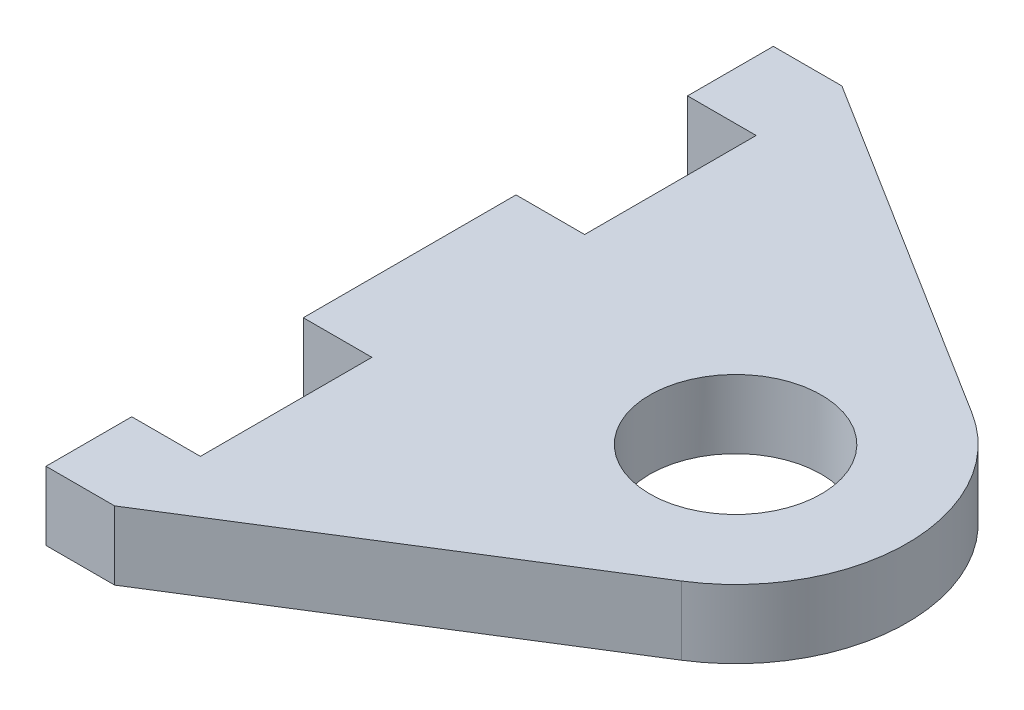
SolidWorks part; units mm, degrees
ref_plane "Front Plane" through (0, 0, 0) normal (0, 0, 1) x (1, 0, 0)
ref_plane "Top Plane" through (0, 0, 0) normal (0, 1, 0) x (1, 0, 0)
ref_plane "Right Plane" through (0, 0, 0) normal (1, 0, 0) x (0, 0, -1)
sketch "Sketch1" plane through (0, 0, 0) normal (0, 1, 0) x (1, 0, 0)
  line L1 (0, 0) -> (20, 0)
  line L2 (0, 0) -> (0, 50)
  line L3 (0, 50) -> (20, 50)
  line L4 (20, 0) -> (20, 50)
  dimension "D1" = 50
  dimension "D2" = 20
extrude "Boss-Extrude2" add sketch "Sketch1" along normal blind 4
sketch "Sketch3" plane through (0, 4, 0) normal (0, 1, 0) x (1, 0, 0)
  line L0 (7.85, 10.95) -> (6.4, 25)
  line L1 (6.4, 25) -> (7.85, 39.05)
  line L2 (12.15, 39.05) -> (13.6, 25)
  line L3 (13.6, 25) -> (12.15, 10.95)
  line L4 (6.4, 25) -> (13.6, 25) construction
  line L5 (20, 50) -> (0, 50) construction
  line L6 (0, 50) -> (0, 0) construction
  arc A0 (12.15, 39.05) -> (7.85, 39.05) centre (10, 39.05) ccw
  arc A1 (7.85, 10.95) -> (12.15, 10.95) centre (10, 10.95) ccw
  point P12 (10, 50)
  point P15 (0, 25)
  dimension "D1" = 4.3
  dimension "D2" = 4.3
  dimension "D3" = 28.1
  dimension "D4" = 14.05
  dimension "D5" = 7.2
  dimension "D6" = 3.6
  dimension "D7" = 3.6
extrude "Cut-Extrude1" cut sketch "Sketch3" against normal blind 2
sketch "Sketch7" plane through (0, 4, 0) normal (0, 1, 0) x (1, 0, 0)
  line L0 (17.1141, 39.7659) -> (18.6, 25)
  line L1 (18.6, 25) -> (17.1141, 10.2341)
  line L4 (10, 46.2) -> (0, 46.2)
  line L5 (0, 50) -> (0, 0) construction
  line L6 (10, 3.8) -> (0, 3.8)
  line L7 (0, 3.8) -> (0, 0)
  line L8 (20, 50) -> (0, 50)
  line L9 (20, 50) -> (20, 0)
  line L10 (20, 0) -> (0, 0)
  line L11 (0, 50) -> (0, 46.2)
  arc A0 (17.1141, 39.7659) -> (10, 46.2) centre (10, 39.05) ccw
  arc A1 (10, 3.8) -> (17.1141, 10.2341) centre (10, 10.95) ccw
  arc A3 (12.15, 39.05) -> (7.85, 39.05) centre (10, 39.05) ccw construction
  arc A4 (7.85, 10.95) -> (12.15, 10.95) centre (10, 10.95) ccw construction
  dimension "D1" = 5
  dimension "D2" = 5
  dimension "D3" = 5
extrude "Cut-Extrude2" cut sketch "Sketch7" against normal through all both and the other way through all
sketch "Sketch8" plane through (0, 0, 0) normal (0, -1, 0) x (1, 0, 0)
  line L1 (0, -46.2) -> (-64.2367, -46.2)
  line L2 (0, -46.2) -> (0, -3.8)
  line L3 (0, -3.8) -> (-64.2367, -3.8)
  line L4 (-64.2367, -46.2) -> (-64.2367, -3.8)
extrude "Boss-Extrude4" add sketch "Sketch8" against normal blind 4
sketch "Sketch9" plane through (0, 2, 0) normal (0, 1, 0) x (1, 0, 0)
  circle A0 centre (10, 25) radius 1.7
  dimension "D1" = 3.4
  dimension "D2" = 3.6
extrude "Cut-Extrude4" cut sketch "Sketch9" against normal blind 4
sketch "Sketch10" plane through (0, 0, 0) normal (0, -1, 0) x (1, 0, 0)
  line L0 (-64.2367, -46.2) -> (10, -46.2) construction
  line L1 (-64.2367, -3.8) -> (-11, -3.8)
  line L2 (-64.2367, -3.8) -> (-64.2367, -46.2)
  line L3 (-64.2367, -46.2) -> (-11, -46.2)
  line L4 (-11, -3.8) -> (-11, -46.2)
  circle A0 centre (10, -25) radius 1.7
  dimension "D1" = 21
extrude "Cut-Extrude5" cut sketch "Sketch10" against normal blind 4
sketch "Sketch11" plane through (0, 0, 0) normal (0, -1, 0) x (1, 0, 0)
  line L0 (-11, -46.2) -> (10, -46.2) construction
  line L1 (-11, -3.8) -> (-5, -3.8)
  line L2 (-11, -3.8) -> (-11, -46.2)
  line L3 (-11, -46.2) -> (-5, -46.2)
  line L4 (-5, -3.8) -> (-5, -46.2)
  dimension "D1" = 6
extrude "Boss-Extrude5" add sketch "Sketch11" along normal blind 62.2
sketch "Sketch13" plane through (-5, 0, 0) normal (1, 0, 0) x (0, 0, -1)
  line L0 (46.2, -62.2) -> (46.2, 0) construction
  line L1 (3.8, -62.2) -> (46.2, -62.2)
  line L2 (3.8, -62.2) -> (3.8, -58.2)
  line L3 (3.8, -58.2) -> (46.2, -58.2)
  line L4 (46.2, -62.2) -> (46.2, -58.2)
  dimension "D1" = 4
extrude "Boss-Extrude6" add sketch "Sketch13" along normal blind 30
sketch "Sketch14" plane through (0, -58.2, 0) normal (0, 1, 0) x (1, 0, 0)
  line L0 (-5, 46.2) -> (-5, 3.8) construction
  line L2 (-5, 3.8) -> (15.3097, 16.5261)
  line L3 (-5, 46.2) -> (15.3097, 33.4739)
  circle A0 centre (10, 25) radius 5
  arc A1 (15.3097, 16.5261) -> (15.3097, 33.4739) centre (10, 25) ccw
  line M6 (-5, 3.8) -> (25, 3.8)
  line M7 (25, 3.8) -> (25, 46.2)
  line M8 (25, 46.2) -> (-5, 46.2)
  dimension "D1" = 10
  dimension "D4" = 20
  dimension "D2" = 15
  dimension "D3" = 21.2
extrude "Cut-Extrude6" cut sketch "Sketch14" against normal blind 30 contours A1 L2 L3 M6 M7 M8 | A0 region at (5.4307, -58.2, -9.7229) region at (10, -58.2, -25)
sketch "Sketch15" plane through (0, 0, -3.8) normal (0, 0, 1) x (1, 0, 0)
  line L0 (-5, -62.2) -> (-11, -62.2) construction
  line L1 (-11, 4) -> (-9, 4)
  line L2 (-11, 4) -> (-11, -62.2)
  line L3 (-11, -62.2) -> (-9, -62.2)
  line L4 (-9, 4) -> (-9, -62.2)
  dimension "D1" = 4
extrude "Cut-Extrude7" cut sketch "Sketch15" against normal through all both and the other way through all
sketch "Sketch16" plane through (-5, 0, 0) normal (1, 0, 0) x (0, 0, -1)
  line L0 (3.8, 0) -> (10, -19.1)
  line L2 (10, -39.1) -> (3.8, -58.2)
  line L4 (46.2, -58.2) -> (40, -39.1)
  line L6 (40, -19.1) -> (46.2, 0)
  line L8 (40, -19.1) -> (30, -19.1)
  line L9 (30, -19.1) -> (30, -39.1)
  line L10 (30, -39.1) -> (40, -39.1)
  line L11 (10, -39.1) -> (20, -39.1)
  line L12 (20, -39.1) -> (20, -19.1)
  line L13 (20, -19.1) -> (10, -19.1)
  line L14 (46.2, -58.2) -> (46.2, 0) construction
  line L16 (3.8, 0) -> (3.8, -58.2)
  line L17 (46.2, -58.2) -> (46.2, 0)
  dimension "D1" = 10
  dimension "D2" = 10
  dimension "D3" = 10
  dimension "D4" = 6.2
  dimension "D5" = 20
  dimension "D6" = 19.1
extrude "Cut-Extrude8" cut sketch "Sketch16" against normal through all both and the other way through all
sketch "Sketch17" plane through (0, 0, -3.8) normal (0, 0, 1) x (1, 0, 0)
  line L1 (-9, -58.2) -> (54.5905, -58.2)
  line L2 (-9, -58.2) -> (-9, 25.9168)
  line L3 (-9, 25.9168) -> (54.5905, 25.9168)
  line L4 (54.5905, -58.2) -> (54.5905, 25.9168)
extrude "Cut-Extrude9" cut sketch "Sketch17" against normal through all both and the other way through all
sketch "Sketch18" plane through (0, -58.2, 0) normal (0, 1, 0) x (1, 0, 0)
  line L0 (-9, 46.2) -> (-9, 3.8) construction
  line L1 (-9, 41.2) -> (-5, 41.2)
  line L2 (-9, 41.2) -> (-9, 31.2)
  line L3 (-9, 31.2) -> (-5, 31.2)
  line L4 (-5, 41.2) -> (-5, 31.2)
  line L6 (-9, 18.8) -> (-5, 18.8)
  line L7 (-9, 18.8) -> (-9, 8.8)
  line L8 (-9, 8.8) -> (-5, 8.8)
  line L9 (-5, 18.8) -> (-5, 8.8)
  dimension "D1" = 5
  dimension "D2" = 10
  dimension "D3" = 5
  dimension "D4" = 10
  dimension "D5" = 4
extrude "Cut-Extrude10" cut sketch "Sketch18" against normal blind 10
